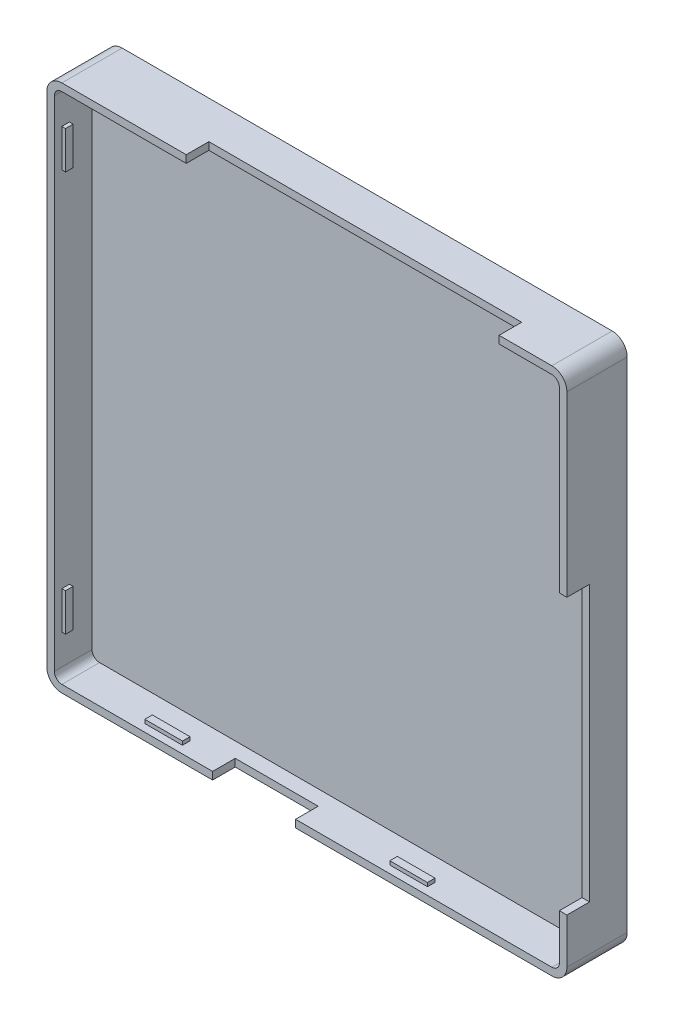
SolidWorks part; units mm, degrees
ref_plane "Plan de face" through (0, 0, 0) normal (0, 0, 1) x (1, 0, 0)
ref_plane "Plan de dessus" through (0, 0, 0) normal (0, 1, 0) x (1, 0, 0)
ref_plane "Plan de droite" through (0, 0, 0) normal (1, 0, 0) x (0, 0, -1)
sketch "Esquisse1" plane through (0, 0, 0) normal (0, 0, 1) x (1, 0, 0)
  line L1 (2, 0) -> (67, 0)
  line L2 (0, 2) -> (0, 68.1)
  line L3 (2, 70.1) -> (67, 70.1)
  line L4 (69, 2) -> (69, 68.1)
  arc A0 (2, 0) -> (0, 2) centre (2, 2) cw
  arc A1 (67, 0) -> (69, 2) centre (67, 2) ccw
  arc A2 (67, 70.1) -> (69, 68.1) centre (67, 68.1) cw
  arc A3 (0, 68.1) -> (2, 70.1) centre (2, 68.1) cw
  point P7 (0, 0)
  point P10 (69, 0)
  point P15 (0, 70.1)
  dimension "D3" = 2
  dimension "D1" = 70.1
  dimension "D2" = 69
extrude "Boss.-Extru.1" add sketch "Esquisse1" along normal blind 8
sketch "Esquisse3" plane through (0, 0, 8) normal (0, 0, 1) x (1, 0, 0)
  line L8 (2, 1) -> (67, 1)
  line L9 (68, 2) -> (68, 68.1)
  line L10 (67, 69.1) -> (2, 69.1)
  line L11 (1, 68.1) -> (1, 2)
  line L12 (2, 1) -> (67, 1)
  line L13 (68, 2) -> (68, 68.1)
  line L14 (67, 69.1) -> (2, 69.1)
  line L15 (1, 68.1) -> (1, 2)
  arc A8 (1, 2) -> (2, 1) centre (2, 2) ccw
  arc A9 (67, 1) -> (68, 2) centre (67, 2) ccw
  arc A10 (68, 68.1) -> (67, 69.1) centre (67, 68.1) ccw
  arc A11 (2, 69.1) -> (1, 68.1) centre (2, 68.1) ccw
  arc A12 (1, 2) -> (2, 1) centre (2, 2) ccw
  arc A13 (67, 1) -> (68, 2) centre (67, 2) ccw
  arc A14 (68, 68.1) -> (67, 69.1) centre (67, 68.1) ccw
  arc A15 (2, 69.1) -> (1, 68.1) centre (2, 68.1) ccw
  dimension "D1" = 1
extrude "Enlèv. mat.-Extru.1" cut sketch "Esquisse3" against normal blind 5
sketch "Esquisse4" plane through (0, 69.1, 0) normal (0, -1, 0) x (1, 0, 0)
  line L0 (67, 3) -> (2, 3) construction
  line L1 (8.1797, 6) -> (13.1797, 6)
  line L2 (8.1797, 6) -> (8.1797, 7)
  line L3 (8.1797, 7) -> (13.1797, 7)
  line L4 (13.1797, 6) -> (13.1797, 7)
  dimension "D1" = 3
  dimension "D2" = 1
  dimension "D3" = 5
extrude "Boss.-Extru.3" add sketch "Esquisse4" along normal blind 0.489 contours L1 L4 L3 L2
sketch "Esquisse5" plane through (68, 0, 0) normal (-1, 0, 0) x (0, 0, 1)
  line L0 (3, 2) -> (3, 68.1) construction
  line L1 (6, 65.1) -> (7, 65.1)
  line L2 (6, 65.1) -> (6, 60.1)
  line L3 (6, 60.1) -> (7, 60.1)
  line L4 (7, 65.1) -> (7, 60.1)
  line L5 (3, 68.1) -> (8, 68.1) construction
  dimension "D1" = 1
  dimension "D2" = 5
  dimension "D3" = 3
  dimension "D4" = 3
extrude "Boss.-Extru.4" add sketch "Esquisse5" along normal blind 0.489
sketch "Esquisse6" plane through (1, 0, 0) normal (1, 0, 0) x (0, 0, -1)
  line L0 (-3, 68.1) -> (-8, 68.1) construction
  line L1 (-6, 64.1) -> (-7, 64.1)
  line L2 (-6, 64.1) -> (-6, 59.1)
  line L3 (-6, 59.1) -> (-7, 59.1)
  line L4 (-7, 64.1) -> (-7, 59.1)
  line L5 (-3, 68.1) -> (-3, 2) construction
  dimension "D1" = 1
  dimension "D2" = 5
  dimension "D3" = 4
  dimension "D4" = 3
extrude "Boss.-Extru.5" add sketch "Esquisse6" along normal blind 0.489
sketch "Esquisse7" plane through (1, 0, 0) normal (1, 0, 0) x (0, 0, -1)
  line L0 (-3, 68.1) -> (-3, 2) construction
  line L1 (-6, 6) -> (-7, 6)
  line L2 (-6, 6) -> (-6, 11)
  line L3 (-6, 11) -> (-7, 11)
  line L4 (-7, 6) -> (-7, 11)
  line L5 (-3, 2) -> (-8, 2) construction
  dimension "D1" = 5
  dimension "D2" = 1
  dimension "D3" = 3
  dimension "D4" = 4
extrude "Boss.-Extru.6" add sketch "Esquisse7" along normal blind 0.489
sketch "Esquisse8" plane through (0, 1, 0) normal (0, 1, 0) x (1, 0, 0)
  line L0 (2, -3) -> (67, -3) construction
  line L1 (12, -6) -> (17, -6)
  line L2 (12, -6) -> (12, -7)
  line L3 (12, -7) -> (17, -7)
  line L4 (17, -6) -> (17, -7)
  line L5 (2, -3) -> (2, -8) construction
  point P6 (12, -6.5)
  dimension "D1" = 1
  dimension "D2" = 5
  dimension "D3" = 3
  dimension "D4" = 10
extrude "Boss.-Extru.7" add sketch "Esquisse8" along normal blind 0.489
sketch "Esquisse9" plane through (0, 1, 0) normal (0, 1, 0) x (1, 0, 0)
  line L0 (2, -3) -> (67, -3) construction
  line L1 (49.5, -6) -> (44.5, -6)
  line L2 (49.5, -6) -> (49.5, -7)
  line L3 (49.5, -7) -> (44.5, -7)
  line L4 (44.5, -6) -> (44.5, -7)
  line L5 (67, -3) -> (67, -8) construction
  dimension "D1" = 5
  dimension "D2" = 1
  dimension "D3" = 3
  dimension "D4" = 17.5
extrude "Boss.-Extru.8" add sketch "Esquisse9" along normal blind 0.489
sketch "Esquisse10" plane through (68, 0, 0) normal (-1, 0, 0) x (0, 0, 1)
  line L0 (3, 2) -> (8, 2) construction
  line L1 (5, 8) -> (8, 8)
  line L2 (5, 8) -> (5, 44.5)
  line L3 (5, 44.5) -> (8, 44.5)
  line L4 (8, 8) -> (8, 44.5)
  line L5 (3, 2) -> (3, 68.1) construction
  dimension "D1" = 36.5
  dimension "D2" = 6
  dimension "D3" = 3
  dimension "D4" = 2
extrude "Enlèv. mat.-Extru.3" cut sketch "Esquisse10" against normal through all contours L2 L1 L4 L3
sketch "Esquisse11" plane through (0, 69.1, 0) normal (0, -1, 0) x (1, 0, 0)
  line L0 (67, 3) -> (67, 8) construction
  line L1 (60, 5) -> (18.5, 5)
  line L2 (60, 5) -> (60, 8)
  line L3 (60, 8) -> (18.5, 8)
  line L4 (18.5, 5) -> (18.5, 8)
  line L5 (67, 3) -> (2, 3) construction
  dimension "D1" = 7
  dimension "D2" = 41.5
  dimension "D3" = 3
  dimension "D4" = 2
extrude "Enlèv. mat.-Extru.4" cut sketch "Esquisse11" against normal through all
sketch "Esquisse12" plane through (0, 1, 0) normal (0, 1, 0) x (1, 0, 0)
  line L0 (2, -3) -> (2, -8) construction
  line L1 (22, -5) -> (33, -5)
  line L2 (22, -5) -> (22, -8)
  line L3 (22, -8) -> (33, -8)
  line L4 (33, -5) -> (33, -8)
  line L5 (2, -3) -> (67, -3) construction
  dimension "D1" = 11
  dimension "D2" = 20
  dimension "D3" = 3
  dimension "D4" = 2
extrude "Enlèv. mat.-Extru.5" cut sketch "Esquisse12" against normal through all
ref_plane "Plan3" through (2, 1, 3) normal (1, 0, 0) x (0, 0, -1)
